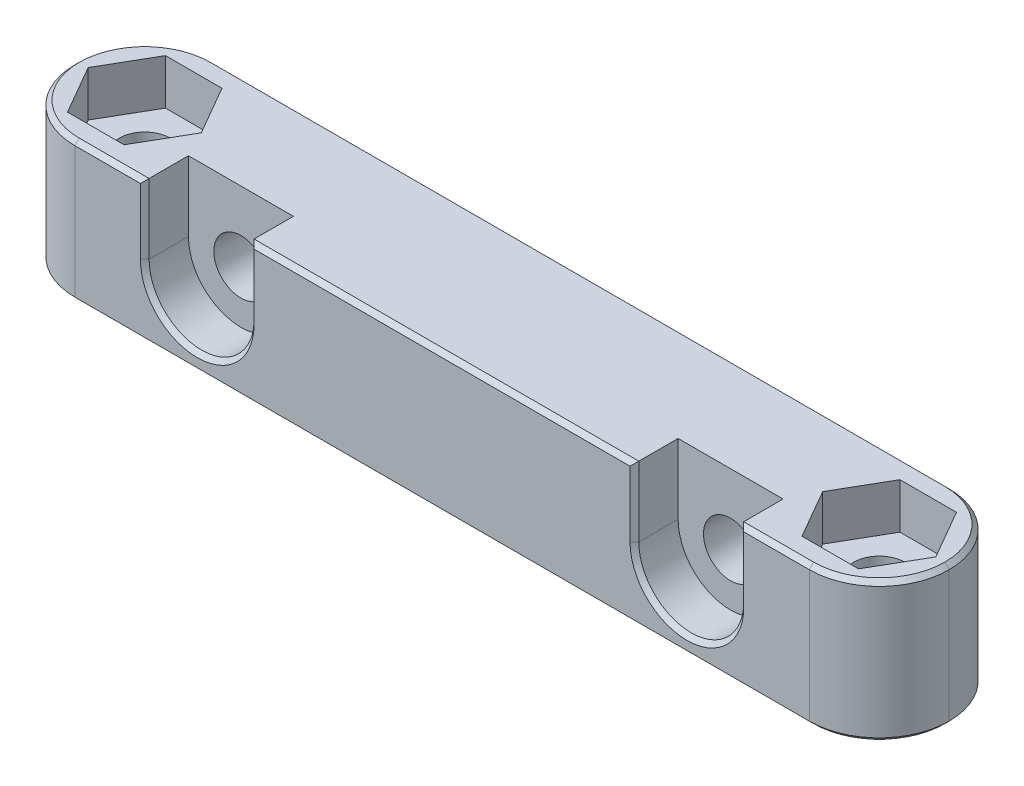
SolidWorks part; units mm, degrees
ref_plane "Płaszczyzna przednia" through (0, 0, 0) normal (0, 0, 1) x (1, 0, 0)
ref_plane "Płaszczyzna górna" through (0, 0, 0) normal (0, 1, 0) x (1, 0, 0)
ref_plane "Płaszczyzna prawa" through (0, 0, 0) normal (1, 0, 0) x (0, 0, -1)
sketch "Szkic1" plane through (0, 0, 0) normal (0, 0, 1) x (1, 0, 0)
  line L0 (-14, 0) -> (14, 0) construction
  line L1 (-25, -4) -> (25, -4)
  line L2 (-25, -4) -> (-25, 4)
  line L3 (-25, 4) -> (25, 4)
  line L4 (25, -4) -> (25, 4)
  line L5 (-25, -4) -> (25, 4) construction
  line L6 (-25, 4) -> (25, -4) construction
  circle A0 centre (-14, 0) radius 1.55
  circle A1 centre (14, 0) radius 1.55
  point P0 (0, 0)
  dimension "D3" = 3.1
  dimension "D1" = 50
  dimension "D2" = 8
  dimension "D4" = 28
extrude "Dodanie-wyciągnięcie1" add sketch "Szkic1" along normal blind 4 and the other way blind 4
sketch "Szkic2" plane through (0, 4, 0) normal (0, 1, 0) x (1, 0, 0)
  line L0 (-21, 0) -> (21, 0) construction
  line L1 (-25, 4) -> (-25, -4) construction
  circle A0 centre (-21, 0) radius 1.45
  circle A1 centre (21, 0) radius 1.45
  point P2 (0, 0)
  dimension "D1" = 2.9
  dimension "D2" = 4
extrude "Wytnij-wyciągnięcie1" cut sketch "Szkic2" against normal through all
sketch "Szkic3" plane through (0, 4, 0) normal (0, 1, 0) x (1, 0, 0)
  line L0 (0, 4) -> (0, -4) construction
  line L1 (-17.7668, 0) -> (-19.3834, 2.8)
  line L2 (-19.3834, 2.8) -> (-22.6166, 2.8)
  line L3 (-22.6166, 2.8) -> (-24.2332, 0)
  line L4 (-24.2332, 0) -> (-22.6166, -2.8)
  line L5 (-22.6166, -2.8) -> (-19.3834, -2.8)
  line L6 (-19.3834, -2.8) -> (-17.7668, 0)
  line L7 (25, 4) -> (-25, 4) construction
  line L8 (25, -4) -> (-25, -4) construction
  line L9 (19.3834, -2.8) -> (17.7668, 0)
  line L10 (22.6166, -2.8) -> (19.3834, -2.8)
  line L11 (24.2332, 0) -> (22.6166, -2.8)
  line L12 (22.6166, 2.8) -> (24.2332, 0)
  line L13 (19.3834, 2.8) -> (22.6166, 2.8)
  line L14 (17.7668, 0) -> (19.3834, 2.8)
  circle A0 centre (-21, 0) radius 2.8 construction
  circle A1 centre (21, 0) radius 2.8 construction
  point P1 (-21, -2.8)
  dimension "D1" = 5.6
extrude "Wytnij-wyciągnięcie2" cut sketch "Szkic3" against normal blind 2.6
sketch "Szkic4" plane through (0, 0, 4) normal (0, 0, 1) x (1, 0, 0)
  circle A0 centre (-14, 0) radius 3
  circle A1 centre (14, 0) radius 3
  dimension "D1" = 6
extrude "Wytnij-wyciągnięcie3" cut sketch "Szkic4" against normal blind 2.5
fillet "Zaokrąglenie1" radius 4 4 edges at (25, 0, -4) (25, 0, 4) (-25, 0, 4) (-25, 0, -4)
sketch "Szkic5" plane through (0, 0, 4) normal (0, 0, 1) x (1, 0, 0)
  line L0 (-17, 0) -> (-11, 0)
  line L1 (-17, 0) -> (-17, 4)
  line L2 (-11, 0) -> (-11, 4)
  line L3 (-17, 4) -> (-11, 4)
  line L4 (11, 0) -> (17, 0)
  line L5 (11, 0) -> (11, 4)
  line L6 (17, 0) -> (17, 4)
  line L7 (11, 4) -> (17, 4)
  line L8 (21, 4) -> (-21, 4) construction
  circle A0 centre (-14, 0) radius 3 construction
  circle A1 centre (14, 0) radius 3 construction
  circle A2 centre (14, 0) radius 3 construction
  point P16 (17, 2.7171)
  point P17 (17, 4)
  point P20 (-11, 4)
extrude "Wytnij-wyciągnięcie4" cut sketch "Szkic5" against normal up to surface (2.5 mm away) up to face at (-11, 0, 1.5)
chamfer "Sfazowanie1" distance 0.25 angle 45 22 edges at (0, -4, -4) (0, 4, -4) (-12.45, 0, -4) (15.55, 0, -4) (23.8284, 4, -2.8284) (-23.8284, 4, -2.8284) (23.8284, 4, 2.8284) (-23.8284, 4, 2.8284) (-19, 4, 4) (19, 4, 4) (-23.8284, -4, -2.8284) (23.8284, -4, -2.8284) (-23.8284, -4, 2.8284) (23.8284, -4, 2.8284) (0, -4, 4) (14, -3, 4) (-14, -3, 4) (17, 2, 4) (11, 2, 4) (0, 4, 4) (-11, 2, 4) (-17, 2, 4)
